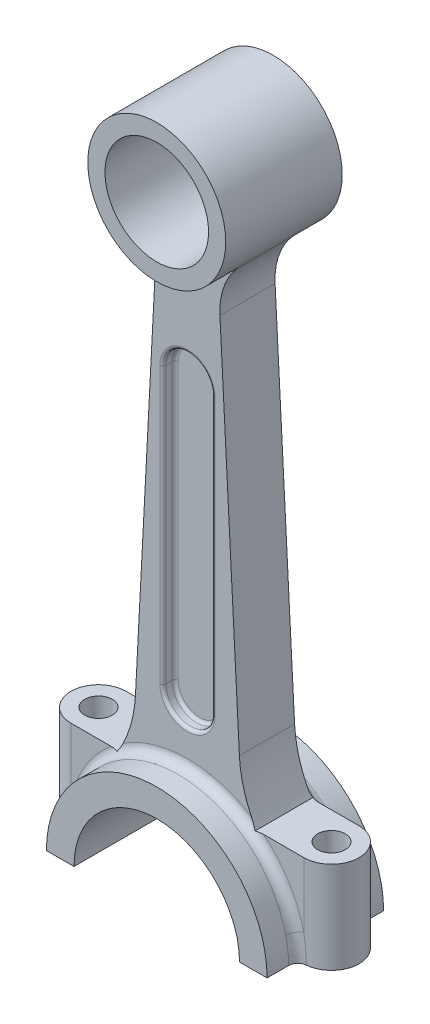
SolidWorks part; units mm, degrees
ref_plane "Front Plane" through (0, 0, 0) normal (0, 0, 1) x (1, 0, 0)
ref_plane "Top Plane" through (0, 0, 0) normal (0, 1, 0) x (1, 0, 0)
ref_plane "Right Plane" through (0, 0, 0) normal (1, 0, 0) x (0, 0, -1)
sketch "Sketch2" plane through (0, 0, 0) normal (0, 0, 1) x (1, 0, 0)
  line L0 (0, 0) -> (0, -174.2) construction
  line L1 (-10, -20.1556) -> (-17.8497, -169.9368)
  line L2 (10, -20.1556) -> (17.8497, -169.9368)
  line L3 (-36, -201.2) -> (-27, -201.2)
  line L4 (27, -201.2) -> (36, -201.2)
  circle A0 centre (0, 0) radius 22.5
  circle A1 centre (0, 0) radius 16.9
  arc A2 (36, -201.2) -> (-36, -201.2) centre (0, -201.2) ccw
  arc A3 (27, -201.2) -> (-27, -201.2) centre (0, -201.2) ccw
  dimension "D1" = 45
  dimension "D2" = 33.8
  dimension "D3" = 72
  dimension "D4" = 54
  dimension "D5" = 201.2
  dimension "D6" = 20
  dimension "D7" = 6
extrude "Boss-Extrude1" add sketch "Sketch2" along normal mid plane 38 contours A1 A0 | A2 A3 | A2 L3 A3 L4 region at (-11.5231, 18.5805, 0) region at (0, -166.005, 0)
extrude "Boss-Extrude2" add sketch "Sketch2<3>" along normal mid plane 18 contours A0 L0 A2 L2 | L0 A0 L1 A2 region at (7.1843, -100.8455, 0) region at (-7.1843, -100.8455, 0)
sketch "Sketch2<3>" plane through (0, 0, 0) normal (0, 0, 1) x (1, 0, 0) same geometry as "Sketch2"
sketch "Sketch3" plane through (0, 0, 9) normal (0, 0, 1) x (1, 0, 0)
  line L0 (0, 0) -> (0, -201.2) construction
  line L1 (0, -145.6) -> (0, -55.6) construction
  line L2 (-8, -145.6) -> (-8, -55.6)
  line L3 (8, -145.6) -> (8, -55.6)
  arc A0 (-8, -145.6) -> (8, -145.6) centre (0, -145.6) ccw
  arc A1 (8, -55.6) -> (-8, -55.6) centre (0, -55.6) ccw
  point P6 (0, -100.6)
  dimension "D2" = 8
  dimension "D1" = 90
extrude "Cut-Extrude2" cut sketch "Sketch3" against normal blind 4
mirror "Mirror1" about plane through (0, 0, 0) normal (0, 0, 1) of "Cut-Extrude2"
fillet "Fillet2" radius 1 16 edges at (0, -153.6, 9) (-8, -100.6, 9) (0, -47.6, 9) (0, -153.6, -9) (-8, -100.6, -9) (0, -47.6, -9) (-8, -100.6, 5) (0, -47.6, 5) (8, -100.6, 5) (0, -153.6, 5) (8, -100.6, -5) (0, -47.6, -5) (-8, -100.6, -5) (0, -153.6, -5) (8, -100.6, 9) (8, -100.6, -9)
fillet "Fillet3" radius 40 2 edges at (17.8497, -169.9368, 0) (-17.8497, -169.9368, 0)
fillet "Fillet4" radius 22.5 2 edges at (-10, -20.1556, 0) (10, -20.1556, 0)
ref_plane "Plane2" through (0, -171.2, 0) normal (0, -1, 0) x (-1, 0, 0)
sketch "Sketch5" plane through (0, -171.2, 0) normal (0, -1, 0) x (-1, 0, 0)
  line L0 (38, 0) -> (-38, 0) construction
  line L1 (38, -9) -> (-38, -9)
  line L2 (38, 9) -> (-38, 9)
  arc A0 (38, -9) -> (38, 9) centre (38, 0) ccw
  arc A1 (-38, 9) -> (-38, -9) centre (-38, 0) ccw
  point P2 (0, 0)
  dimension "D2" = 9
  dimension "D1" = 76
extrude "Boss-Extrude5" add sketch "Sketch5" along normal up to surface (30 mm away) up to face at (-31.5, -201.2, 0)
sketch "Sketch9" plane through (0, 0, 9) normal (0, 0, 1) x (1, 0, 0)
  line L0 (-27, -201.2) -> (27, -201.2)
  arc A0 (27, -201.2) -> (-27, -201.2) centre (0, -201.2) ccw
extrude "Cut-Extrude3" cut sketch "Sketch9" against normal through all
sketch "Sketch10" plane through (0, -171.2, 0) normal (0, 1, 0) x (1, 0, 0)
  circle A0 centre (-38, 0) radius 4.5
  circle A1 centre (38, 0) radius 4.5
  dimension "D1" = 9
  dimension "D2" = 9
extrude "Cut-Extrude4" cut sketch "Sketch10" against normal through all
fillet "Fillet5" radius 3 2 edges at (0, -165.2, 9) (0, -165.2, -9)
